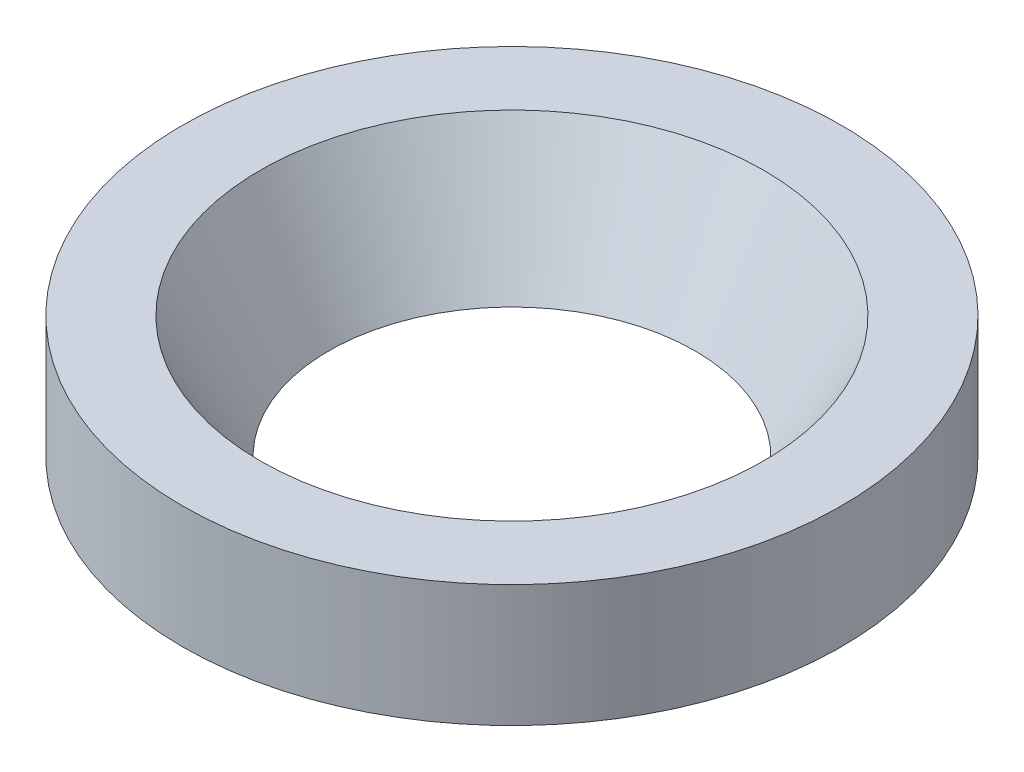
SolidWorks part; units mm, degrees
material "6061 Alloy"
ref_plane "Front Plane" through (0, 0, 0) normal (0, 0, 1) x (1, 0, 0)
ref_plane "Top Plane" through (0, 0, 0) normal (0, 1, 0) x (1, 0, 0)
ref_plane "Right Plane" through (0, 0, 0) normal (1, 0, 0) x (0, 0, -1)
sketch "Sketch1" plane through (0, 0, 0) normal (0, 1, 0) x (1, 0, 0)
  circle A0 centre (0, 0) radius 3
  circle A1 centre (0, 0) radius 5.4
  dimension "D1" = 6
  dimension "D2" = 10.8
extrude "Boss-Extrude1" add sketch "Sketch1" along normal blind 2
chamfer "Chamfer1" distance 1.125 distance2 2 1 edges at (0, 2, 3) first distance on face at (0, 2, 5.4)
